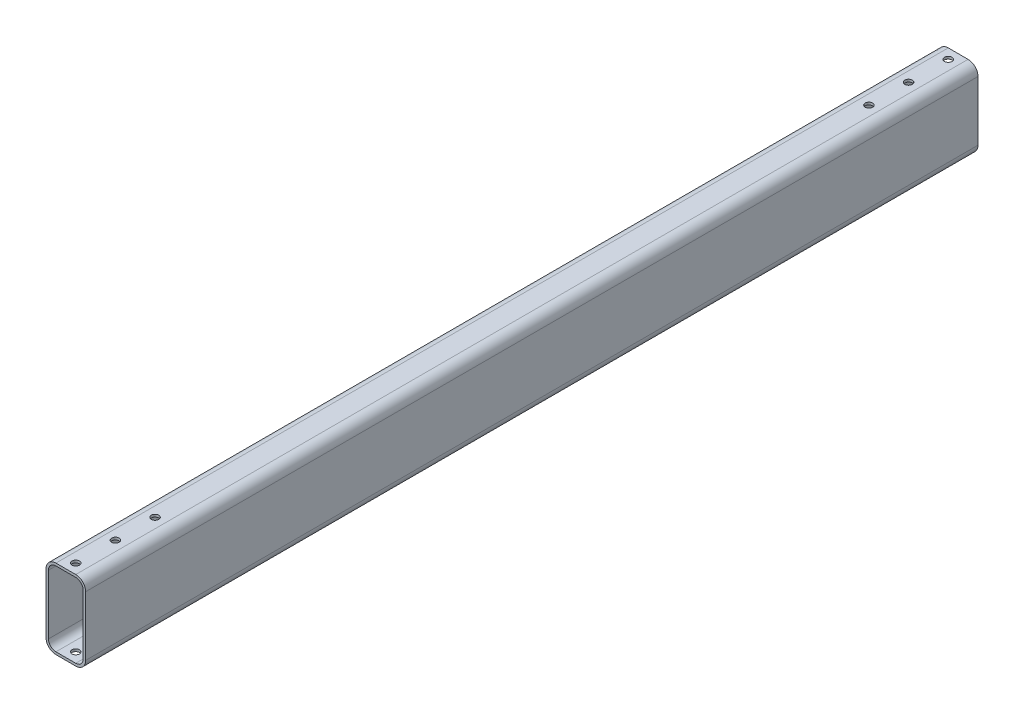
SolidWorks part; units mm, degrees
material "6061-T6 (SS)"
ref_plane "Front Plane" through (0, 0, 0) normal (0, 0, 1) x (1, 0, 0)
ref_plane "Top Plane" through (0, 0, 0) normal (0, 1, 0) x (1, 0, 0)
ref_plane "Right Plane" through (0, 0, 0) normal (1, 0, 0) x (0, 0, -1)
sketch "Sketch1" plane through (0, 0, 0) normal (0, 0, 1) x (1, 0, 0)
  line L1 (-6.35, -25.4) -> (6.35, -25.4)
  line L2 (-12.7, -19.05) -> (-12.7, 19.05)
  line L3 (-6.35, 25.4) -> (6.35, 25.4)
  line L4 (12.7, -19.05) -> (12.7, 19.05)
  line L5 (-12.7, -25.4) -> (12.7, 25.4) construction
  line L6 (-12.7, 25.4) -> (12.7, -25.4) construction
  arc A0 (-12.7, -19.05) -> (-6.35, -25.4) centre (-6.35, -19.05) ccw
  arc A1 (6.35, -25.4) -> (12.7, -19.05) centre (6.35, -19.05) ccw
  arc A2 (6.35, 25.4) -> (12.7, 19.05) centre (6.35, 19.05) cw
  arc A3 (-12.7, 19.05) -> (-6.35, 25.4) centre (-6.35, 19.05) cw
  point P0 (0, 0)
  dimension "D3" = 6.35
  dimension "D1" = 50.8
  dimension "D2" = 25.4
extrude "Extrude-Thin1" add sketch "Sketch1" along normal blind 571.5 thin thin type one direction reverse wall 1.5875
hole_wizard "3/16 (0.1875) Diameter Hole1" positions "3DSketch1" profile "Sketch3" hole size "3/16" standard "ANSI Inch" end condition through all
sketch3d "3DSketch1"
  line L1 (6.35, 25.4, 0) -> (-6.35, 25.4, 0) construction
  line L6 (0, 25.4, 571.5) -> (0, 25.4, 0) construction
  line L7 (6.35, 25.4, 571.5) -> (-6.35, 25.4, 571.5) construction
  point P57 (0, 25.4, 6.35)
  point P59 (0, 25.4, 31.75)
  point P61 (0, 25.4, 57.15)
  point P63 (0, 25.4, 539.75)
  point P65 (0, 25.4, 514.35)
  point P67 (0, 25.4, 565.15)
  dimension "D1" = 25.4
  dimension "D2" = 25.4
  dimension "D3" = 6.35
  dimension "D4" = 25.4
  dimension "D5" = 25.4
  dimension "D6" = 6.35
sketch "Sketch3" plane through (0, 25.4, 565.15) normal (1, 0, 0) x (0, 0, 1)
  line L0 (0, 0) -> (0, 50.8)
  line L1 (0, 50.8) -> (2.3812, 50.8)
  line L2 (2.3812, 50.8) -> (2.3812, 0)
  line L5 (2.3812, 0) -> (0, 0)
  line L11 (0, -6.35) -> (0, 107.95) construction
  dimension "Thru Hole Dia." = 4.7625
  dimension "Thru Hole Depth" = 50.8
